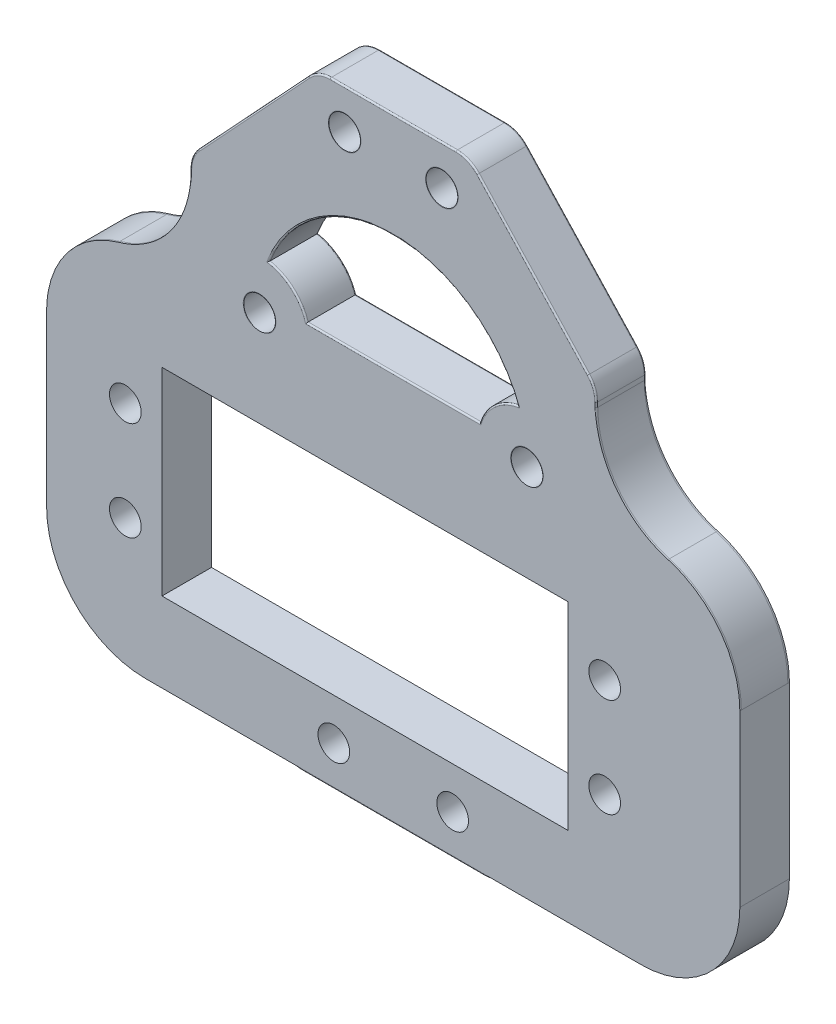
SolidWorks part; units mm, degrees
ref_plane "Front Plane" through (0, 0, 0) normal (0, 0, 1) x (1, 0, 0)
ref_plane "Top Plane" through (0, 0, 0) normal (0, 1, 0) x (1, 0, 0)
ref_plane "Right Plane" through (0, 0, 0) normal (1, 0, 0) x (0, 0, -1)
sketch "Sketch1" plane through (0, 0, 0) normal (0, 0, 1) x (1, 0, 0)
  line L0 (0, 0) -> (0, 62) construction
  line L1 (11, 0) -> (-11, 0)
  line L2 (-11, 0) -> (-20.5, 17.5997)
  line L3 (-20.5, 17.5997) -> (-20.5, 48.1997)
  line L4 (-20.5, 48.1997) -> (-7.6596, 62)
  line L5 (-7.6596, 62) -> (7.6596, 62)
  line L6 (20.5, 48.1997) -> (7.6596, 62)
  line L7 (11, 0) -> (20.5, 17.5997)
  line L8 (20.5, 17.5997) -> (20.5, 48.1997)
  line L9 (7.5, 17.5997) -> (20.5, 17.5997) construction
  line L10 (13.5, 37.8997) -> (-13.5, 37.8997) construction
  line L11 (-8.7303, 39.3997) -> (8.7303, 39.3997)
  line L12 (8.7303, 36.3997) -> (-8.7303, 36.3997) construction
  line L13 (8.7303, 36.3997) -> (8.7303, 39.3997) construction
  line L14 (8.7303, 39.3997) -> (-8.7303, 39.3997) construction
  line L15 (-8.7303, 36.3997) -> (-8.7303, 39.3997) construction
  line L16 (8.7303, 36.3997) -> (-8.7303, 39.3997) construction
  line L17 (8.7303, 39.3997) -> (-8.7303, 36.3997) construction
  line L18 (8.7303, 36.3997) -> (-8.7303, 36.3997)
  line L19 (13.5, 37.8997) -> (11.7867, 28.8079) construction
  line L20 (-12.5741, 32.9862) -> (-12.5741, 17.5997)
  circle A0 centre (-13.5, 37.8997) radius 1.5
  circle A1 centre (-4.9096, 58) radius 1.5
  circle A2 centre (-6, 4) radius 1.5
  circle A3 centre (6, 4) radius 1.5
  circle A4 centre (13.5, 37.8997) radius 1.5
  circle A5 centre (4.9096, 58) radius 1.5
  circle A6 centre (7.5, 17.5997) radius 8.5
  circle A7 centre (13.5, 37.8997) radius 5 construction
  circle A8 centre (-13.5, 37.8997) radius 5 construction
  circle A9 centre (7.5, 17.5997) radius 12 construction
  arc A10 (-12.5741, 42.8132) -> (12.5741, 42.8132) centre (0, 37.8997) cw
  arc A11 (12.5741, 42.8132) -> (8.7303, 39.3997) centre (13.5, 37.8997) ccw
  arc A12 (-12.5741, 42.8132) -> (-8.7303, 39.3997) centre (-13.5, 37.8997) cw
  arc A13 (-8.7303, 36.3997) -> (-12.5741, 32.9862) centre (-13.5, 37.8997) cw
  arc A14 (8.7303, 36.3997) -> (12.5741, 32.9862) centre (13.5, 37.8997) ccw
  arc A15 (11.7867, 28.8079) -> (12.5741, 32.9862) centre (12.1804, 30.8971) ccw
  arc A16 (11.7867, 28.8079) -> (-4.5, 17.5997) centre (7.5, 17.5997) ccw
  arc A17 (-12.5741, 17.5997) -> (-4.5, 17.5997) centre (-8.537, 17.5997) ccw
  dimension "D2" = 3
  dimension "D10" = 17
  dimension "D19" = 13.5
  dimension "D1" = 62
  dimension "D3" = 6
  dimension "D4" = 4
  dimension "D5" = 20
  dimension "D6" = 30.6
  dimension "D7" = 7
  dimension "D8" = 10.3
  dimension "D9" = 11
  dimension "D11" = 2.75
  dimension "D12" = 4
  dimension "D13" = 18.85
  dimension "D14" = 20.5
  dimension "D15" = 13
  dimension "D20" = 3
  dimension "D16" = 3.5
  dimension "D17" = 3.5
  dimension "D18" = 3.5
extrude "Boss-Extrude1" add sketch "Sketch1" along normal blind 5
fillet "Fillet1" radius 3 8 edges at (-20.5, 48.1997, 2.5) (-7.6596, 62, 2.5) (7.6596, 62, 2.5) (20.5, 48.1997, 2.5) (-20.5, 17.5997, 2.5) (-11, 0, 2.5) (20.5, 17.5997, 2.5) (11, 0, 2.5)
fillet "Fillet2" radius 0.15 68 edges at (0.6971, 27.4851, 0) (-8.537, 13.5627, 0) (-12.5741, 25.293, 0) (-10.1799, 34.1611, 0) (0, 36.3997, 0) (10.1799, 34.1611, 0) (14.2695, 30.5034, 0) (3.4096, 58, 0) (4.5, 4, 0) (-4.5, 4, 0) (-12, 37.8997, 0) (-20.4086, 17.6228, 0) (-15.9951, 9.2539, 0) (-10.7472, 0.4237, 0) (0, 0, 0) (10.7472, 0.4237, 0) (15.9951, 9.2539, 0) (20.4086, 17.6228, 0) (20.5, 32.6888, 0) (20.2919, 48.1179, 0) (14.1229, 55.0535, 0) (7.551, 61.7505, 0) (0, 62, 0) (-7.551, 61.7505, 0) (-14.1229, 55.0535, 0) (-20.2919, 48.1179, 0) (-20.5, 32.6888, 0) (-3.4096, 58, 0) (16, 17.5997, 0) (10.1799, 41.6383, 0) (0, 39.3997, 0) (-10.1799, 41.6383, 0) (0, 51.3997, 0) (12, 37.8997, 0) (0, 36.3997, 5) (-10.1799, 34.1611, 5) (-12.5741, 25.293, 5) (-8.537, 13.5627, 5) (0.6971, 27.4851, 5) (14.2695, 30.5034, 5) (10.1799, 34.1611, 5) (16, 17.5997, 5) (-4.5, 4, 5) (-3.4096, 58, 5) (-12, 37.8997, 5) (-7.551, 61.7505, 5) (0, 62, 5) (7.551, 61.7505, 5) (14.1229, 55.0535, 5) (20.2919, 48.1179, 5) (20.5, 32.6888, 5) (20.4086, 17.6228, 5) (15.9951, 9.2539, 5) (10.7472, 0.4237, 5) (0, 0, 5) (-10.7472, 0.4237, 5) (-15.9951, 9.2539, 5) (-20.4086, 17.6228, 5) (-20.5, 32.6888, 5) (-20.2919, 48.1179, 5) (-14.1229, 55.0535, 5) (0, 39.3997, 5) (10.1799, 41.6383, 5) (0, 51.3997, 5) (-10.1799, 41.6383, 5) (4.5, 4, 5) (12, 37.8997, 5) (3.4096, 58, 5)
sketch "Sketch2" plane through (0, 0, 5) normal (0, 0, 1) x (1, 0, 0)
  line L0 (-8.8417, 36.5497) -> (8.8417, 36.5497) construction
  line L1 (-35, 36.5497) -> (-14.1538, 36.5497)
  line L2 (-35, 36.5497) -> (-35, 0.15)
  line L3 (-35, 0.15) -> (35, 0.15)
  line L4 (35, 36.5497) -> (35, 0.15)
  line L5 (-35, 36.5497) -> (35, 0.15) construction
  line L6 (-35, 0.15) -> (35, 36.5497) construction
  line L7 (-9.2102, 0.15) -> (9.2102, 0.15) construction
  line L8 (-12.8462, 36.5497) -> (12.8462, 36.5497)
  line L9 (14.1538, 36.5497) -> (35, 36.5497)
  circle A1 centre (13.5, 37.8997) radius 1.5 construction
  arc A3 (14.1538, 36.5497) -> (12.8462, 36.5497) centre (13.5, 37.8997) ccw construction
  arc A4 (12.8462, 36.5497) -> (14.1538, 36.5497) centre (13.5, 37.8997) ccw
  circle A5 centre (-13.5, 37.8997) radius 1.5 construction
  arc A6 (-14.1538, 36.5497) -> (-12.8462, 36.5497) centre (-13.5, 37.8997) ccw
  circle A7 centre (6, 4) radius 1.5 construction
  circle A8 centre (-6, 4) radius 1.5 construction
  circle A9 centre (6, 4) radius 1.5
  circle A10 centre (-6, 4) radius 1.5
  circle A11 centre (7.5, 17.5997) radius 8.65 construction
  circle A12 centre (7.5, 17.5997) radius 8.65
  point P4 (0, 18.3499)
  dimension "D1" = 70
extrude "Boss-Extrude2" add sketch "Sketch2" against normal blind 5
sketch "Sketch3" plane through (0, 0, 5) normal (0, 0, 1) x (1, 0, 0)
  line L1 (-23.35, 8.1997) -> (17.65, 8.1997)
  line L2 (-23.35, 8.1997) -> (-23.35, 28.1997)
  line L3 (-23.35, 28.1997) -> (17.65, 28.1997)
  line L4 (17.65, 8.1997) -> (17.65, 28.1997)
  line L5 (-23.35, 8.1997) -> (17.65, 28.1997) construction
  line L6 (-23.35, 28.1997) -> (17.65, 8.1997) construction
  circle A0 centre (7.5, 17.5997) radius 8.65 construction
  circle A2 centre (7.5, 17.5997) radius 8.65 construction
  point P4 (-2.85, 18.1997)
  dimension "D1" = 20
  dimension "D2" = 41
  dimension "D3" = 10.35
  dimension "D4" = 0.6
extrude "Cut-Extrude1" cut sketch "Sketch3" against normal through all
sketch "Sketch4" plane through (0, 0, 5) normal (0, 0, 1) x (1, 0, 0)
  line L0 (-23.35, 28.1997) -> (-23.35, 8.1997) construction
  line L2 (17.65, 28.1997) -> (-23.35, 28.1997) construction
  circle A0 centre (-27.05, 23.1997) radius 1.5
  circle A1 centre (-27.05, 13.1997) radius 1.5
  circle A2 centre (21.35, 13.1997) radius 1.5
  circle A3 centre (21.35, 23.1997) radius 1.5
  point P10 (-2.85, 28.1997)
  point P15 (-23.35, 18.1997)
  dimension "D1" = 10
  dimension "D5" = 3
  dimension "D2" = 48.4
  dimension "D3" = 5
  dimension "D4" = 24.2
extrude "Cut-Extrude2" cut sketch "Sketch4" against normal through all
fillet "Fillet3" radius 10 6 edges at (20.4561, 36.5497, 4.9561) (20.4561, 36.5497, 0.0439) (-20.4561, 36.5497, 0.0439) (-20.4561, 36.5497, 4.9561) (20.5, 36.5497, 2.5) (-20.5, 36.5497, 2.5)
fillet "Fillet4" radius 10 4 edges at (-35, 0.15, 2.5) (-35, 36.5497, 2.5) (35, 0.15, 2.5) (35, 36.5497, 2.5)
hole_wizard "M3 Clearance Hole1" positions "Sketch5" profile "Sketch6" hole size "M3" standard "ANSI Metric" end condition through all
sketch "Sketch5" plane through (0, 0, 5) normal (0, 0, 1) x (1, 0, 0)
  point P0 (-4.9096, 58)
  point P3 (4.9096, 58)
  point P6 (13.5, 37.8997)
  point P9 (-13.5, 37.8997)
  point P12 (-27.05, 23.1997)
  point P15 (-27.05, 13.1997)
  point P18 (-6, 4)
  point P21 (6, 4)
  point P24 (21.35, 13.1997)
  point P27 (21.35, 23.1997)
sketch "Sketch6" plane through (-4.9096, 58, 5) normal (1, 0, 0) x (0, -1, 0)
  line L0 (0, 0) -> (0, 5.0987)
  line L1 (0, 5.0987) -> (1.6, 5.0987)
  line L2 (1.6, 5.0987) -> (1.6, 0)
  line L5 (1.6, 0) -> (0, 0)
  line L11 (0, -6.35) -> (0, 107.95) construction
  dimension "Thru Hole Dia." = 3.2
  dimension "Thru Hole Depth" = 5.0987
